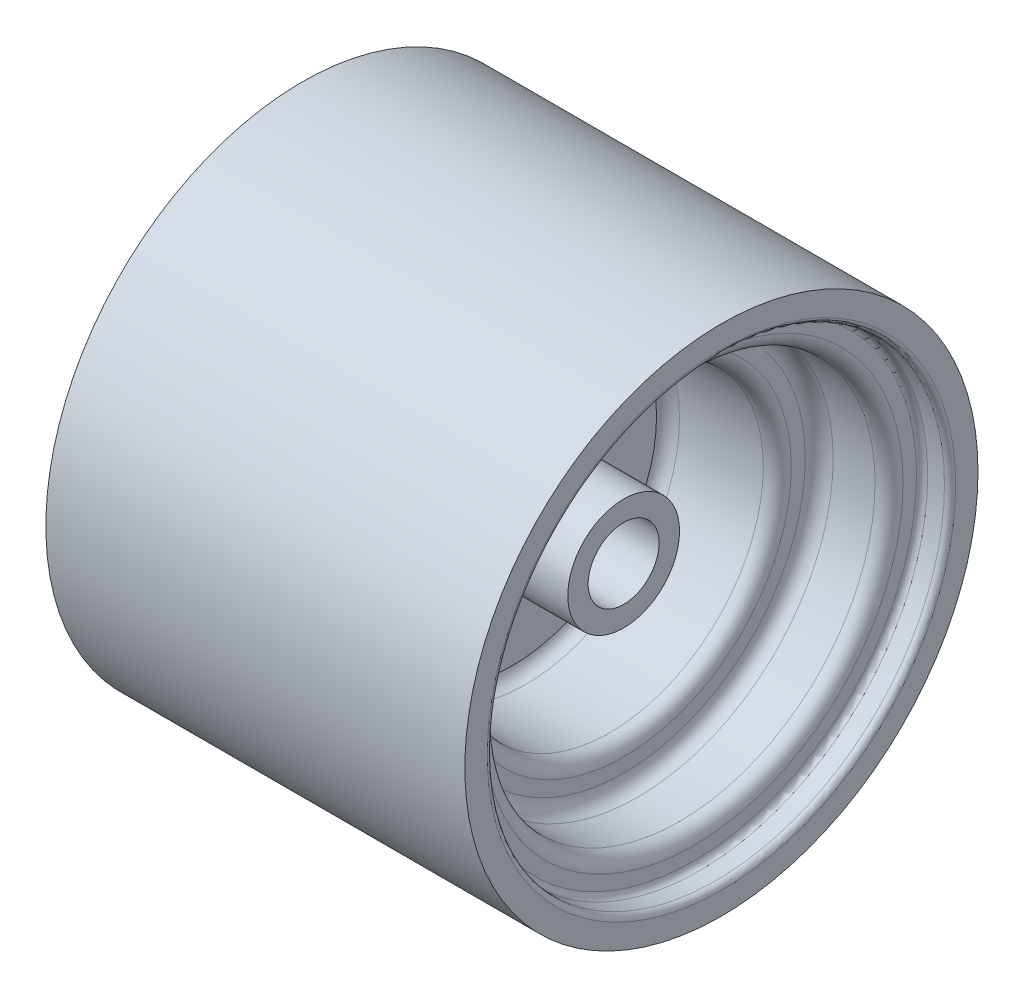
SolidWorks part; units mm, degrees
material "Cast Alloy Steel"
ref_plane "Front Plane" through (0, 0, 0) normal (0, 0, 1) x (1, 0, 0)
ref_plane "Top Plane" through (0, 0, 0) normal (0, 1, 0) x (1, 0, 0)
ref_plane "Right Plane" through (0, 0, 0) normal (1, 0, 0) x (0, 0, -1)
sketch "Sketch1" plane through (0, 0, 0) normal (1, 0, 0) x (0, 0, -1)
  circle A0 centre (0, 0) radius 91.845
extrude "Boss-Extrude1" add sketch "Sketch1" along normal blind 150.24
sketch "Sketch2" plane through (150.24, 0, 0) normal (1, 0, 0) x (0, 0, -1)
  circle A0 centre (0, 0) radius 81.845
extrude "Cut-Extrude1" cut sketch "Sketch2" against normal blind 10
sketch "Sketch3" plane through (140.24, 0, 0) normal (1, 0, 0) x (0, 0, -1)
  circle A0 centre (0, 0) radius 70
extrude "Cut-Extrude2" cut sketch "Sketch3" against normal blind 25
sketch "Sketch4" plane through (115.24, 0, 0) normal (1, 0, 0) x (0, 0, -1)
  circle A0 centre (0, 0) radius 55
extrude "Cut-Extrude3" cut sketch "Sketch4" against normal blind 40
sketch "Sketch5" plane through (75.24, 0, 0) normal (1, 0, 0) x (0, 0, -1)
  circle A0 centre (0, 0) radius 20
extrude "Boss-Extrude3" add sketch "Sketch5" along normal blind 40
ref_plane "Plane1" through (75.24, 0, 0) normal (1, 0, 0) x (0, 0, -1)
sketch "Sketch6" plane through (0, 0, 0) normal (-1, 0, 0) x (0, 0, 1)
  circle A0 centre (0, 0) radius 91.845
extrude "Cut-Extrude4" cut sketch "Sketch6" against normal blind 75
fillet "Fillet1" radius 2 1 edges at (150.24, 0, -81.845)
fillet "Fillet2" radius 5 1 edges at (140.24, 0, -70)
fillet "Fillet3" radius 5 1 edges at (115.24, 0, -70)
fillet "Fillet4" radius 2 1 edges at (140.24, 0, -81.845)
fillet "Fillet5" radius 5 1 edges at (115.24, 0, -55)
fillet "Fillet6" radius 5 1 edges at (75.24, 0, -55)
fillet "Fillet7" radius 2 1 edges at (75.24, 0, -20)
sketch "Sketch7" plane through (115.24, 0, 0) normal (1, 0, 0) x (0, 0, -1)
  circle A0 centre (0, 0) radius 12.7
extrude "Cut-Extrude5" cut sketch "Sketch7" against normal blind 75
mirror "Mirror9" about plane through (75.24, 0, 0) normal (1, 0, 0) of bodies 115
ref_axis "Axis1" through (35.24, 0, 0) along (1, 0, 0)
